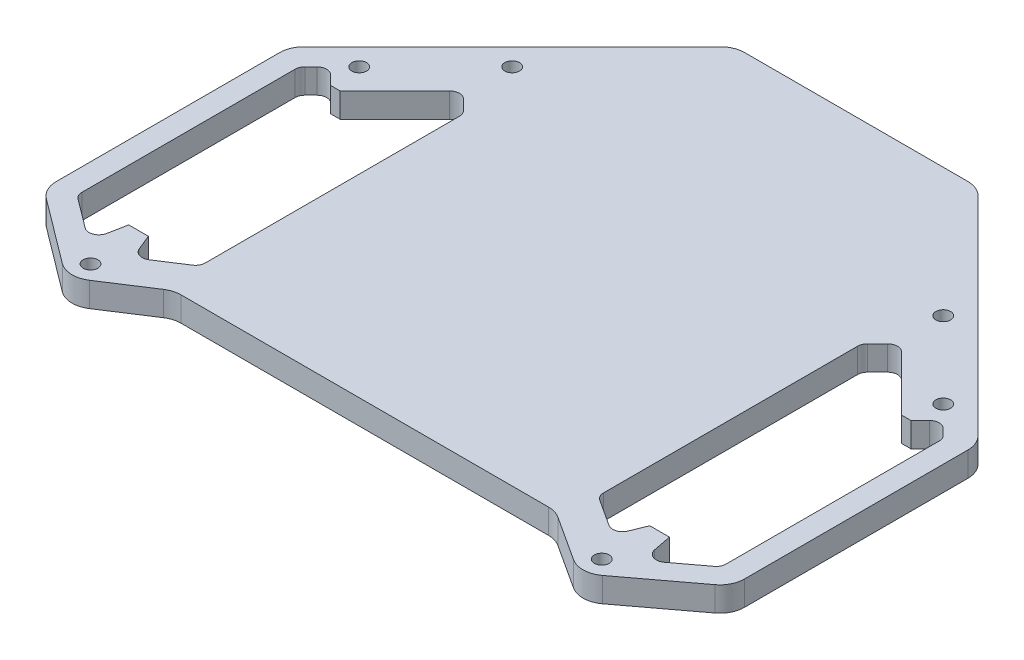
SolidWorks part; units mm, degrees
ref_plane "Front Plane" through (0, 0, 0) normal (0, 0, 1) x (1, 0, 0)
ref_plane "Top Plane" through (0, 0, 0) normal (0, 1, 0) x (1, 0, 0)
ref_plane "Right Plane" through (0, 0, 0) normal (1, 0, 0) x (0, 0, -1)
sketch "Sketch1" plane through (0, 0, 0) normal (0, 1, 0) x (1, 0, 0)
  line L0 (-52.1641, -38.6452) -> (-70, -25.2479)
  line L1 (-70, -25.2479) -> (-70, 24.7523)
  line L2 (-70, 24.7523) -> (-24.7523, 70)
  line L3 (-52.1641, -38.6452) -> (-38.8516, -30)
  line L4 (0, -30) -> (0, 70)
  line L5 (0, -30) -> (-38.8516, -30)
  line L6 (-59.397, 28.2843) -> (-43.8406, 43.8406) construction
  line L7 (-51.9976, -33.7676) -> (-63.9796, -15.3169) construction
  line L8 (-24.7523, 70) -> (0, 70)
  line L9 (0, 0) -> (-85, 0) construction
  line L10 (-43.8406, 43.8406) -> (0, 0) construction
  line L11 (-51.9976, -33.7676) -> (0, 0) construction
  line L12 (-59.0038, 22.1) -> (-57.096, 22.1)
  line L13 (-65.5, 22.1812) -> (-65.5, -23)
  line L14 (-55, -23) -> (-51, -23)
  line L15 (-40.5, 30.6005) -> (-40.5, -23)
  line L16 (-53, 22.1) -> (-53, -23) construction
  line L17 (-65.5, 22.1812) -> (-62.2925, 25.3887)
  line L18 (-62.2925, 25.3887) -> (-59.0038, 22.1)
  line L19 (-57.096, 22.1) -> (-44.5477, 34.6482)
  line L20 (-44.5477, 34.6482) -> (-40.5, 30.6005)
  line L21 (-65.5, -23) -> (-56.3366, -29.883)
  line L22 (-56.3366, -29.883) -> (-55, -23)
  line L23 (-51, -23) -> (-48.7962, -28.3876)
  line L24 (-48.7962, -28.3876) -> (-40.5, -23)
  circle A0 centre (0, 0) radius 85 construction
  circle A1 centre (-43.8406, 43.8406) radius 1.5
  circle A2 centre (-51.9976, -33.7676) radius 1.5
  circle A3 centre (-59.397, 28.2843) radius 1.5
  circle A4 centre (-63.9796, -15.3169) radius 1.5 construction
  dimension "D7" = 3
  dimension "D17" = 170
  dimension "D20" = 12.5
  dimension "D2" = 30
  dimension "D3" = 4
  dimension "D4" = 4
  dimension "D5" = 4.5
  dimension "D6" = 70
  dimension "D8" = 62
  dimension "D9" = 22
  dimension "D10" = 22
  dimension "D11" = 25
  dimension "D12" = 45.1
  dimension "D13" = 53
  dimension "D14" = 45
  dimension "D15" = 33
  dimension "D16" = 23
  dimension "D18" = 5
  dimension "D19" = 70
  dimension "D21" = 5
  dimension "D22" = 5
  dimension "D23" = 4
  dimension "D24" = 6
  dimension "D25" = 15
extrude "Boss-Extrude1" add sketch "Sketch1" along normal blind 5
fillet "Fillet1" radius 2 8 edges at (-40.5, 2.5, 23) (-48.7962, 2.5, 28.3876) (-56.3366, 2.5, 29.883) (-65.5, 2.5, 23) (-65.5, 2.5, -22.1812) (-62.2925, 2.5, -25.3887) (-40.5, 2.5, -30.6005) (-44.5477, 2.5, -34.6482)
mirror "Mirror1" about plane through (0, 5, 30) normal (-1, 0, 0) of "Fillet1", "Boss-Extrude1"
sketch "Sketch2" plane through (0, 0, 0) normal (0, 1, 0) x (1, 0, 0)
  line L0 (24.7523, 70) -> (-24.7523, 70) construction
  line L1 (-35, 70) -> (35, 70)
  line L2 (-35, 70) -> (-35, -27)
  line L3 (-35, -27) -> (35, -27)
  line L4 (35, 70) -> (35, -27)
  line L5 (-38.8516, -30) -> (38.8516, -30) construction
  dimension "D1" = 3
  dimension "D2" = 70
  dimension "D3" = 35
extrude "Cut-Extrude1" cut sketch "Sketch2" along normal blind 3
fillet "Fillet2" radius 5 10 edges at (-70, 2.5, 25.2479) (-70, 2.5, -24.7523) (-24.7523, 4, -70) (24.7523, 4, -70) (70, 2.5, -24.7523) (70, 2.5, 25.2479) (38.8516, 2.5, 30) (52.1641, 2.5, 38.6452) (-38.8516, 2.5, 30) (-52.1641, 2.5, 38.6452)
